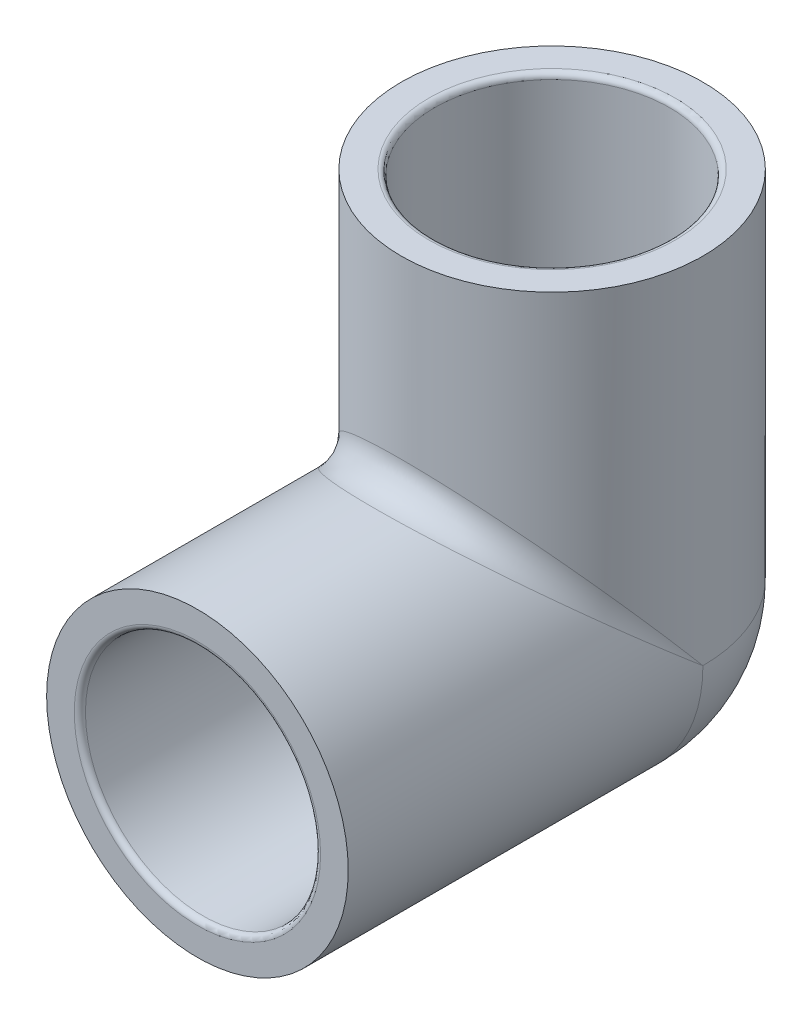
SolidWorks part; units mm, degrees
ref_plane "Front Plane" through (0, 0, 0) normal (0, 0, 1) x (1, 0, 0)
ref_plane "Top Plane" through (0, 0, 0) normal (0, 1, 0) x (1, 0, 0)
ref_plane "Right Plane" through (0, 0, 0) normal (1, 0, 0) x (0, 0, -1)
sketch "Sketch1" plane through (0, 0, 0) normal (0, 0, 1) x (1, 0, 0)
  line L0 (0, 13.716) -> (0, 10.668)
  line L1 (0, -10.668) -> (0, -13.716)
  arc A0 (0, 13.716) -> (0, -13.716) centre (0, 0) ccw
  arc A1 (0, 10.668) -> (0, -10.668) centre (0, 0) ccw
  dimension "D1" = 21.336
  dimension "D2" = 27.432
revolve "Revolve6" add sketch "Sketch1" angle 360 about L0
sketch "Sketch3" plane through (0, 0, 0) normal (0, 0, 1) x (1, 0, 0)
  circle A0 centre (0, 0) radius 13.716
  circle A1 centre (0, 0) radius 10.6934
  dimension "D1" = 21.3868
extrude "Boss-Extrude1" add sketch "Sketch3" along normal blind 32.258
sketch "Sketch4" plane through (0, 0, 0) normal (0, 1, 0) x (1, 0, 0)
  circle A0 centre (0, 0) radius 13.716
  circle A1 centre (0, 0) radius 10.6934
  dimension "D1" = 21.3868
extrude "Boss-Extrude2" add sketch "Sketch4" along normal blind 32.258
sketch "Sketch5" plane through (0, 0, 32.258) normal (0, 0, 1) x (1, 0, 0)
  circle A0 centre (0, 0) radius 10.4394
  circle A1 centre (0, 0) radius 10.6934 construction
  dimension "D1" = 0.254
extrude "Cut-Extrude1" cut sketch "Sketch5" against normal blind 32.258
sketch "Sketch6" plane through (0, 32.258, 0) normal (0, 1, 0) x (1, 0, 0)
  circle A0 centre (0, 0) radius 10.4394
  arc A1 (10.6934, 0) -> (-10.6934, 0) centre (0, 0) ccw construction
  dimension "D1" = 0.254
extrude "Cut-Extrude2" cut sketch "Sketch6" against normal blind 32.258
fillet "Fillet1" radius 2.54 1 edges at (0, 13.716, 13.716)
fillet "Fillet2" radius 0.508 2 edges at (10.6934, 0, 32.258) (0, 32.258, 10.6934)
